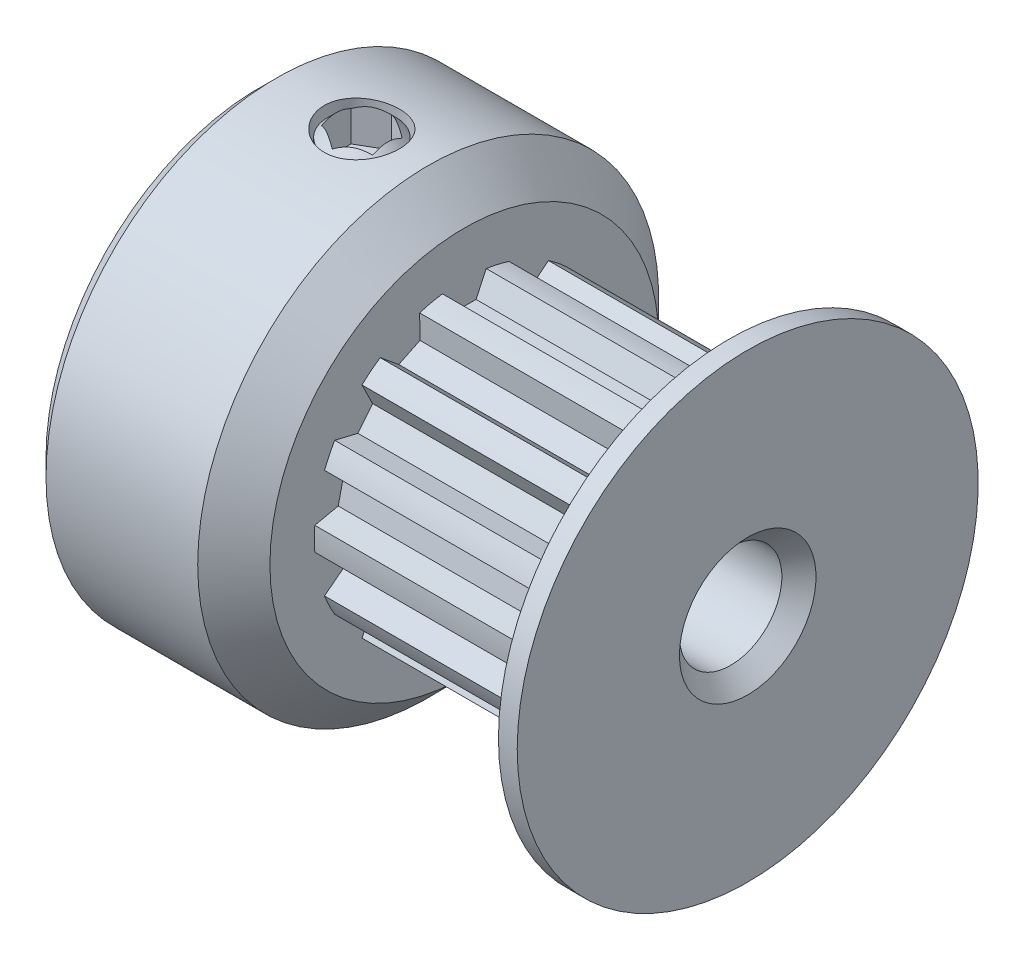
SolidWorks part; units mm, degrees
ref_plane "Front Plane" through (0, 0, 0) normal (0, 0, 1) x (1, 0, 0)
ref_plane "Top Plane" through (0, 0, 0) normal (0, 1, 0) x (1, 0, 0)
ref_plane "Right Plane" through (0, 0, 0) normal (1, 0, 0) x (0, 0, -1)
sketch "Sketch2" plane through (0, 0, 0) normal (1, 0, 0) x (0, 0, -1)
  line L3 (0, 0) -> (0, 3.7245) construction
  line L6 (0, -4.2325) -> (0, -4.55) construction
  line L7 (-0.5715, 4.1937) -> (-0.3452, 3.7085)
  line L8 (0.5715, 4.1937) -> (0.3452, 3.7085)
  line L9 (-0.5715, 4.1937) -> (-0.6416, 4.3441)
  line L10 (0.5715, 4.1937) -> (0.6416, 4.3441)
  line L12 (-0.3452, 3.7085) -> (0.3452, 3.7085)
  line L14 (0, 4.2325) -> (0, 4.55) construction
  line L15 (0, 0) -> (0, -1.143) construction
  circle A0 centre (0, 0) radius 4.55 construction
  circle A1 centre (0, 0) radius 3.7245 construction
  circle A2 centre (0, 0) radius 4.2325 construction
  arc A7 (0.6416, 4.3441) -> (-0.6416, 4.3441) centre (0, 0) ccw
  point P5 (0, 4.3913)
  dimension "D3" = 0.3175
  dimension "D1" = 50
sketch "Sketch1" plane through (0, 0, 0) normal (0, 0, 1) x (1, 0, 0)
  line L0 (-7.15, 0) -> (7.15, 0) construction
  line L1 (-7.15, 1.5) -> (7.15, 1.5)
  line L2 (-7.15, 1.5) -> (-7.15, 6.75)
  line L3 (-7.15, 6.75) -> (-2.207, 6.75)
  line L4 (-2.207, 6.75) -> (-1.15, 5.693)
  line L5 (-1.15, 5.693) -> (-1.15, 4.55)
  line L6 (-1.15, 4.55) -> (6.05, 4.55)
  line L7 (6.05, 4.55) -> (6.05, 5.1215)
  line L8 (6.05, 4.55) -> (7.15, 4.55) construction
  line L9 (6.6, 6.75) -> (7.15, 6.75)
  line L10 (7.15, 6.75) -> (7.15, 1.5)
  line L11 (6.6, 4.55) -> (6.6, 6.75) construction
  line L12 (-4.6785, 6.75) -> (-4.6785, 1.5) construction
  arc A0 (6.05, 5.1215) -> (6.6, 6.75) centre (8.7359, 5.1215) cw
  dimension "Bore Size" = 3
  dimension "Overall Width" = 14.3
  dimension "Inside Width" = 7.2
  dimension "Outside Width" = 8.3
  dimension "Hub Dia" = 13.5
  dimension "OD" = 13.5
  dimension "D1" = 45
  dimension "D2" = 9.1
  dimension "D3" = 1.143
  dimension "D4" = 0.5715
revolve "Revolve1" add sketch "Sketch1" angle 360 mid plane about L0
sketch "Sketch4" plane through (-1.15, 0, 0) normal (1, 0, 0) x (0, 0, -1)
  circle A0 centre (0, 0) radius 4.3913
  circle A1 centre (0, 0) radius 4.55 construction
  circle A2 centre (0, 0) radius 4.55
extrude "Cut-Extrude2" cut sketch "Sketch4" along normal up to surface (7.2 mm away) up to face at (6.05, 0, 4.55)
sketch "Sketch3" plane through (-1.15, 0, 0) normal (1, 0, 0) x (0, 0, -1)
  line L2 (-0.5715, 4.1937) -> (-0.3452, 3.7085) construction
  line L3 (-0.3452, 3.7085) -> (0.3452, 3.7085) construction
  line L4 (0.5715, 4.1937) -> (0.3452, 3.7085) construction
  line L5 (-0.6416, 4.3441) -> (-0.3452, 3.7085)
  line L6 (-0.3452, 3.7085) -> (0.3452, 3.7085)
  line L7 (0.6416, 4.3441) -> (0.3452, 3.7085)
  arc A1 (0.6416, 4.3441) -> (-0.6416, 4.3441) centre (0, 0) ccw construction
  arc A2 (0.6416, 4.3441) -> (-0.6416, 4.3441) centre (0, 0) ccw
extrude "Cut-Extrude1" cut sketch "Sketch3" along normal up to surface (7.2 mm away)
pattern_circular "CirPattern1" count 14 over 360 of "Cut-Extrude1"
sketch "Sketch5" plane through (0, 0, 0) normal (0, 0, 1) x (1, 0, 0)
  line L1 (6.05, 5.1215) -> (6.05, -5.1215) construction
  point P0 (6.05, 0)
sketch "Sketch6" plane through (0, 0, 0) normal (0, 1, 0) x (1, 0, 0)
  line L0 (-7.15, 0) -> (-5.15, 0) construction
  line L1 (-7.15, 6.75) -> (-7.15, -6.75) construction
  line L2 (-1.15, 0) -> (-3.15, 0) construction
  line L3 (-1.15, -0.3452) -> (-1.15, 0.3452) construction
  circle A0 centre (-4.15, 0) radius 1 construction
  circle A1 centre (-4.15, 0) radius 1.1
  dimension "D1" = 0.1
  dimension "SS Dia" = 2
extrude "Cut-Extrude3" cut sketch "Sketch6" along normal through all
sketch "Sketch7" plane through (0, 0, 0) normal (0, 0, 1) x (1, 0, 0)
  line L0 (-4.896, 6.75) -> (-4.15, 6.75)
  line L1 (-5.15, 6.496) -> (-5.15, 2.135)
  line L2 (-5.15, 2.135) -> (-4.896, 1.881)
  line L3 (-4.896, 1.881) -> (-4.15, 1.881)
  line L4 (-4.15, 1.881) -> (-4.15, 6.75) construction
  line L6 (-5.15, 6.496) -> (-4.896, 6.75)
  line L7 (-7.15, 6.75) -> (-2.207, 6.75) construction
  line L8 (-4.15, 6.75) -> (-4.15, 1.881)
  point P0 (-5.15, 6.75)
  point P4 (-5.15, 1.881)
  dimension "D2" = 0.381
revolve "Revolve2" add sketch "Sketch7" angle 360 mid plane about L4
sketch "Sketch8" plane through (0, 6.75, 0) normal (0, 1, 0) x (1, 0, 0)
  line L1 (-4.15, 0.866) -> (-4.9, 0.433)
  line L2 (-4.9, 0.433) -> (-4.9, -0.433)
  line L3 (-4.9, -0.433) -> (-4.15, -0.866)
  line L4 (-4.15, -0.866) -> (-3.4, -0.433)
  line L5 (-3.4, -0.433) -> (-3.4, 0.433)
  line L6 (-3.4, 0.433) -> (-4.15, 0.866)
  circle A0 centre (-4.15, 0) radius 0.75 construction
  dimension "D1" = 1.5
extrude "Cut-Extrude4" cut sketch "Sketch8" against normal blind 1.016
pattern_circular "CirPattern2" [suppressed] count 2 over 90 reverse direction yes of bodies 105
pattern_circular "CirPattern3" [suppressed] count 2 over 90 reverse direction yes of bodies 107
chamfer "Chamfer1" distance 0.5 angle 45 3 edges at (-7.15, 0, 6.75) (-7.15, 0, 1.5) (7.15, 0, 1.5)
ref_axis "Center Axis 1" through (6.65, 0, 0) along (-1, 0, 0)
ref_plane "Contact Plane 1" through (7.15, 0, 0) normal (1, 0, 0) x (0, 0, -1)
ref_plane "Contact Plane 2" through (-7.15, 0, 0) normal (-1, 0, 0) x (0, 0, 1)
equation "\"D3@Sketch2\" = (\"hs@Sketch2\"-\"ht@Sketch2\")/2"
equation "\"D2@Sketch1\" = \"PD@Sketch2\""
equation "\"D3@Sketch1\" = \"hs@Sketch2\""
equation "\"D4@Sketch1\" = \"D3@Sketch1\"/2"
